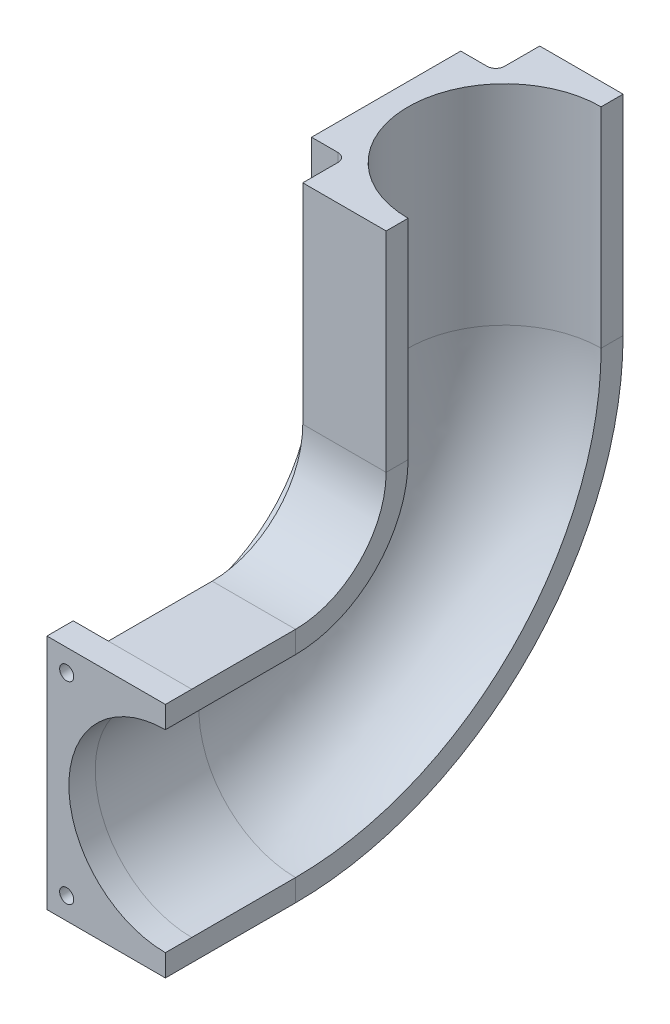
SolidWorks part; units mm, degrees
ref_plane "Front" through (0, 0, 0) normal (0, 0, 1) x (1, 0, 0)
ref_plane "Top" through (0, 0, 0) normal (0, 1, 0) x (1, 0, 0)
ref_plane "Right" through (0, 0, 0) normal (1, 0, 0) x (0, 0, -1)
sketch "草图1" plane through (0, 0, 0) normal (0, 0, 1) x (1, 0, 0)
  line L0 (0, 0) -> (-27, 0)
  line L1 (-27, 0) -> (-27, -54)
  line L2 (-27, -54) -> (0, -54)
  line L3 (0, -54) -> (0, -49)
  line L4 (0, 0) -> (0, -5)
  arc A0 (0, -5) -> (0, -49) centre (0, -27) ccw
  point P9 (0, -56)
  dimension "D1" = 44
  dimension "D2" = 54
  dimension "D3" = 27
extrude "凸台-拉伸1" add sketch "草图1" against normal blind 6
sketch "草图2" plane through (0, 0, -6) normal (0, 0, -1) x (-1, 0, 0)
  line L0 (19, 0) -> (19, -8)
  line L1 (21, -10) -> (27, -10)
  line L2 (19, -54) -> (19, -46)
  line L3 (21, -44) -> (27, -44)
  line L5 (0, 0) -> (0, -5)
  line L6 (0, -49) -> (0, -54)
  line L7 (0, -54) -> (27, -54)
  line L8 (27, -54) -> (27, 0)
  line L9 (27, 0) -> (0, 0)
  line L10 (0, 0) -> (0, -5)
  line L11 (0, -49) -> (0, -54)
  line L12 (0, -54) -> (19, -54)
  line L13 (27, -44) -> (27, -10)
  line L14 (19, 0) -> (0, 0)
  arc A0 (19, -46) -> (21, -44) centre (21, -46) cw
  arc A1 (0, -49) -> (0, -5) centre (0, -27) ccw
  arc A2 (0, -49) -> (0, -5) centre (0, -27) ccw
  arc A3 (21, -10) -> (19, -8) centre (21, -8) cw
  point P17 (19, -10)
  dimension "D4" = 2
  dimension "D2" = 10
  dimension "D3" = 8
  dimension "D1" = 0
sketch "草图3" plane through (0, 0, 0) normal (1, 0, 0) x (0, 0, -1)
  line L0 (6, -27) -> (29.66, -27.0009)
  line L1 (77.3117, 20.6491) -> (77.3117, 68.2991)
  arc A0 (29.66, -27.0009) -> (77.3117, 20.6491) centre (29.6617, 20.6491) ccw
  point P4 (0, 0)
  point P6 (12.7848, -30.2647)
  dimension "D2" = 47.65
  dimension "D1" = 23.66
  dimension "D3" = 47.65
sweep "扫描1" add profiles "草图2" path "草图3"
ref_plane "基准面1" through (0, -27, 0) normal (0, 1, 0) x (1, 0, 0)
sketch "草图4" plane through (0, 0, -6) normal (0, 0, -1) x (-1, 0, 0)
  line L0 (19, 0) -> (27, 0) construction
  line L1 (27, 0) -> (27, -10) construction
  circle A0 centre (22.5, -5) radius 1.605
  dimension "D1" = 3.21
  dimension "D2" = 5
  dimension "D3" = 4.5
extrude "切除-拉伸1" cut sketch "草图4" against normal blind 10
mirror "镜向1" about plane through (0, -27, 0) normal (0, 1, 0) of "切除-拉伸1"
